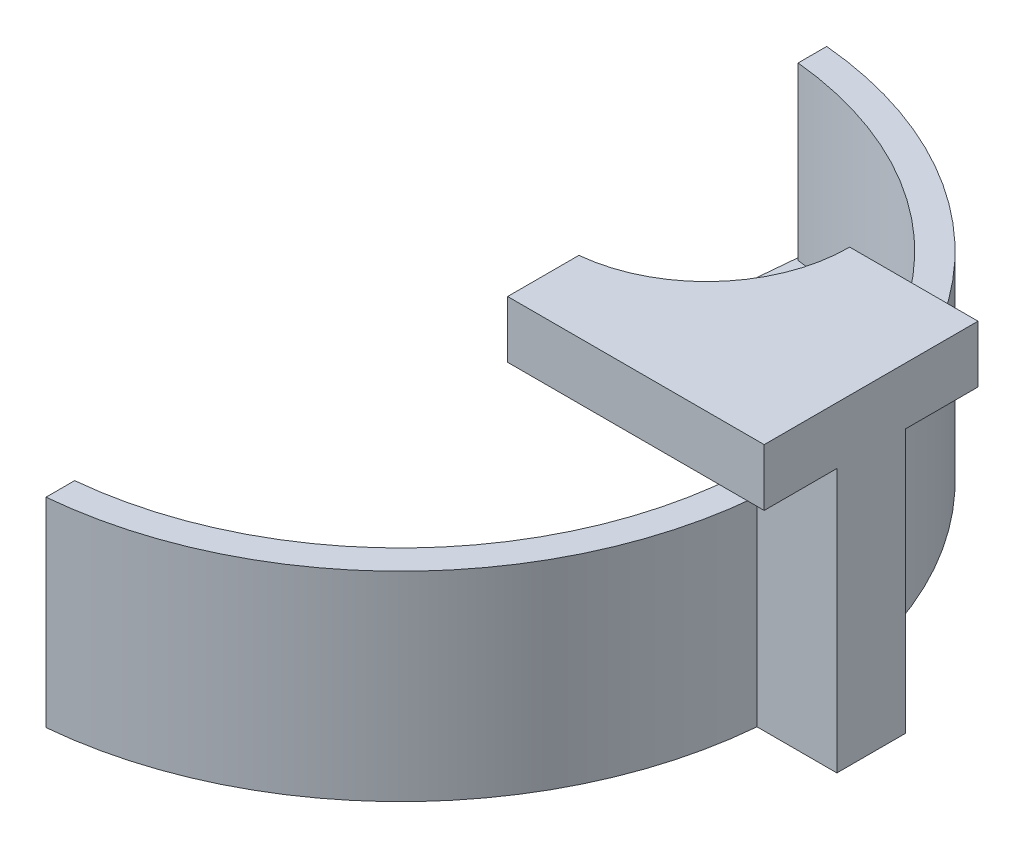
SolidWorks part; units mm, degrees
ref_plane "Front Plane" through (0, 0, 0) normal (0, 0, 1) x (1, 0, 0)
ref_plane "Top Plane" through (0, 0, 0) normal (0, 1, 0) x (1, 0, 0)
ref_plane "Right Plane" through (0, 0, 0) normal (1, 0, 0) x (0, 0, -1)
sketch "Sketch1" plane through (0, 0, 0) normal (0, 1, 0) x (1, 0, 0)
  line L4 (2.5, 27.3861) -> (2.5, 25.3772)
  line L6 (-2.5, 0) -> (2.5, 0) construction
  line L7 (2.5, -25.3772) -> (2.5, -27.3861)
  arc A2 (2.5, -27.3861) -> (2.5, 27.3861) centre (0, 0) ccw
  arc A5 (2.5, -25.3772) -> (2.5, 25.3772) centre (0, 0) ccw
  point P4 (24.3858, 7.4555)
  point P12 (26.2984, 8.0402)
extrude "Boss-Extrude3" add sketch "Sketch1" along normal blind 12
sketch "Sketch2" plane through (0, 0, 0) normal (0, 1, 0) x (1, 0, 0)
  line L0 (2.5, -25.3772) -> (2.5, -27.3861) construction
  line L1 (2.5, 27.3861) -> (1.8636, 20.4151)
  line L2 (2.5, -27.3861) -> (1.8636, -20.4151)
  arc A0 (2.5, 27.3861) -> (2.5, -27.3861) centre (0, 0) cw
  arc A1 (2.5, -27.3861) -> (2.5, 27.3861) centre (0, 0) ccw construction
  arc A2 (1.8636, 20.4151) -> (1.8636, -20.4151) centre (0, 0) cw
  dimension "D1" = 7
extrude "Boss-Extrude4" add sketch "Sketch2" against normal blind 2
sketch "Sketch3" plane through (0, -2, 0) normal (0, -1, 0) x (1, 0, 0)
  line L1 (27, -2.4) -> (33, -2.4)
  line L2 (27, -2.4) -> (27, 2.4)
  line L3 (27, 2.4) -> (33, 2.4)
  line L4 (33, -2.4) -> (33, 2.4)
  line L5 (30, 2.4) -> (30, -2.4) construction
  line L6 (27, 0) -> (33, 0) construction
  point P0 (30, 0)
  dimension "D1" = 30
  dimension "D2" = 4.8
  dimension "D3" = 6
extrude "Boss-Extrude5" add sketch "Sketch3" against normal blind 20
sketch "Sketch4" plane through (0, 18, 0) normal (0, 1, 0) x (1, 0, 0)
  line L0 (33, 2.4) -> (33, -2.4) construction
  line L4 (33, 7.5) -> (33, -7.5)
  line L5 (27, -2.4) -> (27, 2.4) construction
  line L11 (15, 7.5) -> (15, -7.5)
  line L12 (15, -7.5) -> (33, -7.5)
  line L13 (33, 7.5) -> (15, 7.5)
  point P0 (30, 0)
  point P6 (33, 0)
  point P12 (27, 0)
  line M4 (33, -2.4) -> (33, 2.4)
  line M5 (33, 2.4) -> (27, 2.4)
  line M6 (27, 2.4) -> (27, -2.4)
  line M7 (27, -2.4) -> (33, -2.4)
  dimension "D1" = 15
  dimension "D2" = 18
  dimension "D3" = 3
extrude "Boss-Extrude6" add sketch "Sketch4" along normal blind 2.5 and the other way blind 1.5 contours L4 M7 M6 M5 | M7 M4 M5 M6 region at (23.2836, 18, 0) region at (30, 18, 0)
ref_plane "Plane1" through (0, 18.5, 0) normal (0, -1, 0) x (-1, 0, 0)
sketch "Sketch6" plane through (0, 20.5, 0) normal (0, 1, 0) x (1, 0, 0)
  line L0 (15, 7.5) -> (15, -7.5) construction
  line L3 (15, -2.5) -> (15, 7.5)
  line L4 (15, 7.5) -> (24, 7.5)
  arc A0 (15, -2.5) -> (24, 7.5) centre (14.0001, 7.4499) ccw
  dimension "D1" = 10
  dimension "D2" = 5
  dimension "D3" = 9
extrude "Cut-Extrude2" cut sketch "Sketch6" against normal blind 5
ref_plane "Plane2" through (0, 0, -2.4) normal (0, 0, -1) x (-1, 0, 0)
ref_plane "Plane3" through (0, 0, 2.4) normal (0, 0, 1) x (1, 0, 0)
ref_plane "Plane4" through (27, 0, 0) normal (-1, 0, 0) x (0, 0, 1)
